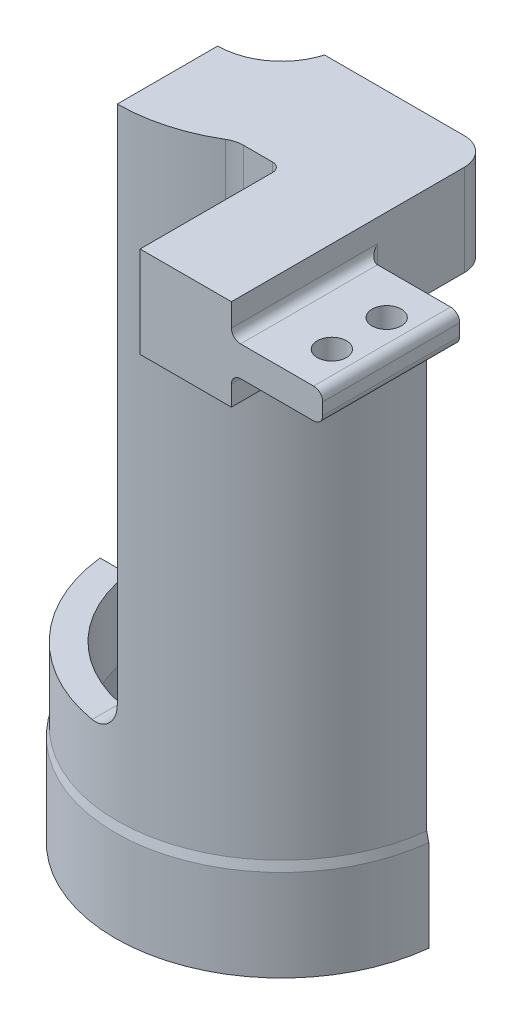
SolidWorks part; units mm, degrees
ref_plane "前视基准面" through (0, 0, 0) normal (0, 0, 1) x (1, 0, 0)
ref_plane "上视基准面" through (0, 0, 0) normal (0, 1, 0) x (1, 0, 0)
ref_plane "右视基准面" through (0, 0, 0) normal (1, 0, 0) x (0, 0, -1)
sketch "草图1" plane through (0, 0, 0) normal (0, 0, 1) x (1, 0, 0)
  line L0 (6.6106, -8) -> (9.6106, -8)
  line L1 (6.6106, 0) -> (12.6106, 0)
  line L4 (12.6106, 0) -> (12.6106, -8)
  line L9 (12.6106, -8) -> (12.8361, -8.9921)
  line L13 (6.6106, 0) -> (-5.3894, 0)
  line L14 (6.6106, -8) -> (6.6106, -60)
  line L15 (6.6106, -60) -> (-5.3894, -60)
  line L16 (-5.3894, 0) -> (-5.3894, -60)
  line L18 (9.6106, -8) -> (11.1606, -14.8201)
  line L23 (11.1606, -14.8201) -> (12.1126, -19.0089)
  line L24 (12.8361, -8.9921) -> (12.8361, -19.0089)
  line L25 (12.1126, -19.0089) -> (12.8361, -19.0089)
  dimension "D1" = 6
  dimension "D2" = 8
  dimension "D3" = 12
revolve "旋转2" add sketch "草图1" angle 180 about L16
sketch "草图2" plane through (0, 0, 0) normal (0, 1, 0) x (1, 0, 0)
  line L0 (-23.3894, 0) -> (12.6106, 0) construction
  circle A0 centre (-5.3894, 0) radius 15
extrude "切除-拉伸2" cut sketch "草图2" against normal blind 60
sketch "草图3" plane through (0, 0, 0) normal (0, 1, 0) x (1, 0, 0)
  line L2 (-5.3894, -15) -> (-5.3894, -18)
  line L3 (9.6106, 0) -> (12.6106, 0)
  line L4 (9.6106, 0) -> (5.6106, 0)
  line L5 (-5.3894, -11) -> (-5.3894, -15)
  line L6 (1.6106, 0) -> (5.6106, 0)
  line L7 (-5.3894, -7) -> (-5.3894, -11)
  arc A2 (-5.3894, -18) -> (12.6106, 0) centre (-5.3894, 0) ccw
  arc A4 (-5.3894, -7) -> (1.6106, 0) centre (-5.3894, 0) ccw
extrude "凸台-拉伸1" add sketch "草图3" along normal blind 60
sketch "草图4" plane through (0, 60, 0) normal (0, 1, 0) x (1, 0, 0)
  line L1 (6.6106, 0) -> (29.6106, 0)
  line L2 (-5.3894, -12) -> (-5.3894, -15)
  line L3 (-5.3894, -15) -> (29.6106, -15)
  line L4 (29.6106, 0) -> (29.6106, -15)
  arc A1 (-5.3894, -12) -> (6.6106, 0) centre (-5.3894, 0) ccw
  dimension "D1" = 15
  dimension "D2" = 35
extrude "凸台-拉伸2" add sketch "草图4" against normal blind 10
sketch "草图8" plane through (0, 0, 15) normal (0, 0, 1) x (1, 0, 0)
  line L0 (4.5605, 50) -> (29.6106, 50) construction
  line L1 (29.6106, 60) -> (9.6106, 60)
  line L2 (29.6106, 60) -> (29.6106, 50)
  line L3 (29.6106, 50) -> (9.6106, 50)
  line L4 (9.6106, 60) -> (9.6106, 50)
  dimension "D1" = 20
extrude "凸台-拉伸3" add sketch "草图8" along normal blind 15.5
sketch "草图9" plane through (29.6106, 0, 0) normal (1, 0, 0) x (0, 0, -1)
  line L1 (-30.5, 60) -> (-15.5, 60)
  line L2 (-30.5, 60) -> (-30.5, 56.5)
  line L3 (-30.5, 56.5) -> (-15.5, 56.5)
  line L4 (-15.5, 60) -> (-15.5, 56.5)
  line L5 (-30.5, 50) -> (-15.5, 50)
  line L6 (-30.5, 50) -> (-30.5, 53.2)
  line L7 (-30.5, 53.2) -> (-15.5, 53.2)
  line L8 (-15.5, 50) -> (-15.5, 53.2)
  dimension "D1" = 15
  dimension "D2" = 15
  dimension "D3" = 3.3
  dimension "D4" = 3.5
extrude "切除-拉伸5" cut sketch "草图9" against normal blind 10
sketch "草图10" plane through (0, 56.5, 0) normal (0, 1, 0) x (1, 0, 0)
  line L0 (29.6106, -30.5) -> (29.6106, -15.5) construction
  line L1 (19.6106, -15.5) -> (29.6106, -15.5) construction
  line L2 (19.6106, -30.5) -> (29.6106, -30.5) construction
  circle A0 centre (26.1106, -26) radius 1.6
  circle A1 centre (26.1106, -20) radius 1.6
  dimension "D1" = 3.5
  dimension "D2" = 4.5
  dimension "D3" = 3.5
  dimension "D4" = 4.5
extrude "切除-拉伸6" cut sketch "草图10" against normal blind 10
fillet "圆角10" radius 1 5 edges at (29.6106, 53.2, 23) (29.6106, 56.5, 23) (19.6106, 53.2, 23) (19.6106, 56.5, 23) (9.6106, 55, 15)
sketch "草图12" plane through (0, 60, 0) normal (0, 1, 0) x (1, 0, 0)
  line L1 (19.6106, -15.5) -> (29.6106, -15.5)
  line L2 (19.6106, -15.5) -> (19.6106, 0)
  line L3 (19.6106, 0) -> (29.6106, 0)
  line L4 (29.6106, -15.5) -> (29.6106, 0)
extrude "切除-拉伸8" cut sketch "草图12" against normal blind 10
fillet "圆角11" radius 1 1 edges at (19.6106, 54.85, 15.5)
sketch "草图13" plane through (0, 60, 0) normal (0, 1, 0) x (1, 0, 0)
  line L1 (19.6106, 0) -> (-36.0678, 0)
  line L2 (19.6106, 0) -> (19.6106, -2)
  line L3 (19.6106, -2) -> (-36.0678, -2)
  line L4 (-36.0678, 0) -> (-36.0678, -2)
  dimension "D1" = 2
extrude "切除-拉伸9" cut sketch "草图13" against normal blind 150
fillet "圆角12" radius 3 3 edges at (4.5605, 55, 15) (9.9727, 50, 9.3811) (19.6106, 55, 2)
fillet "圆角13" radius 3 1 edges at (-5.3894, 0, 16.5)
